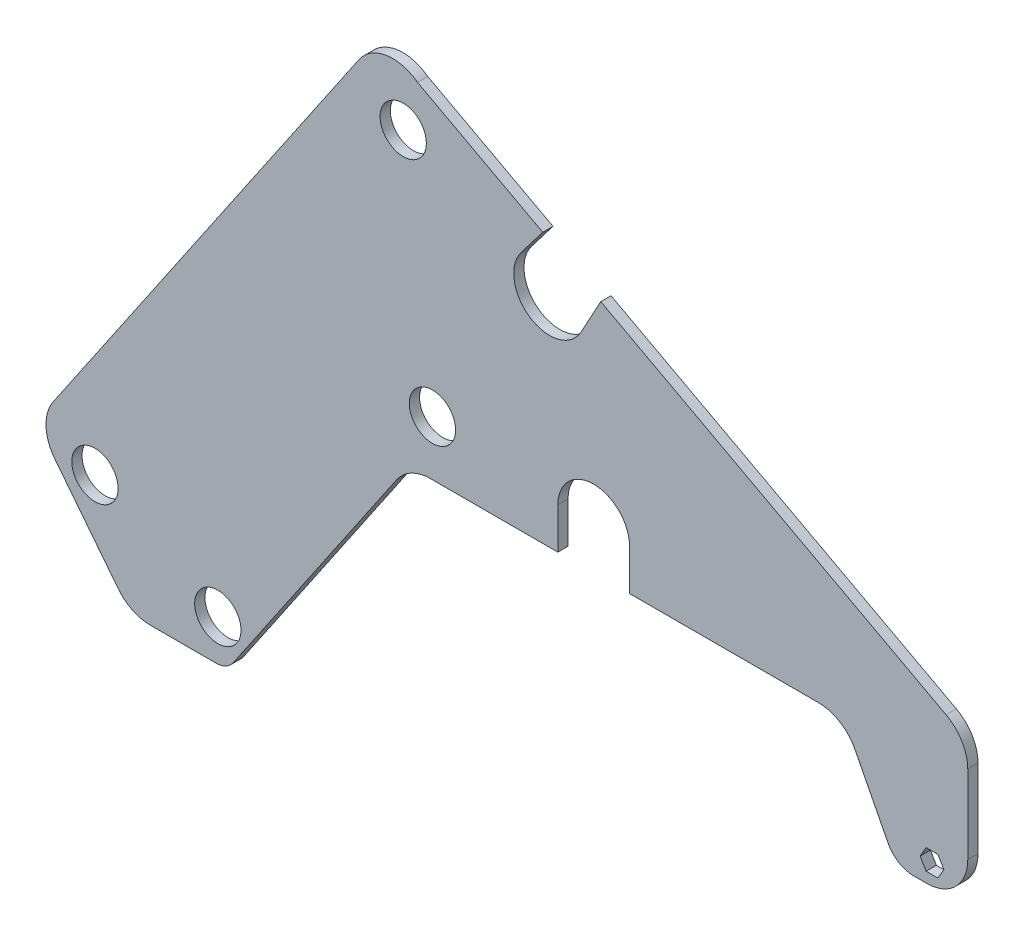
SolidWorks part; units mm, degrees
other "Markup1"
sketch "Sketch1" plane through (-441.7893, 331.8239, 6.35) normal (-0.0431, 0.0102, 0.999) x (0.9985, 0.0354, 0.0427)
sketch "Sketch2" plane through (-413.6701, 343.933, 6.35) normal (-0.0431, 0.0102, 0.999) x (0.9985, 0.0354, 0.0427)
sketch "Sketch3" plane through (-436.3774, 318.5567, 6.35) normal (-0.0431, 0.0102, 0.999) x (0.9985, 0.0354, 0.0427)
sketch "Sketch5" plane through (-436.3774, 318.5567, 6.35) normal (-0.0431, 0.0102, 0.999) x (0.9985, 0.0354, 0.0427)
sketch "Sketch7" plane through (-430.3226, 318.5567, 6.35) normal (-0.0431, 0.0102, 0.999) x (0.9985, 0.0354, 0.0427)
other "Markup2"
sketch "Sketch4" plane through (102.4721, 318.5567, 6.35) normal (0.9364, 0.1073, 0.3342) x (0.3416, -0.0598, -0.9379)
sketch "Sketch6" plane through (102.4721, 318.5567, 6.35) normal (0.9364, 0.1073, 0.3342) x (0.3416, -0.0598, -0.9379)
sketch "Sketch8" plane through (141.2086, 318.5567, 6.35) normal (0.9364, 0.1073, 0.3342) x (0.3416, -0.0598, -0.9379)
ref_plane "Front Plane" through (0, 0, 0) normal (0, 0, 1) x (1, 0, 0)
ref_plane "Top Plane" through (0, 0, 0) normal (0, 1, 0) x (1, 0, 0)
ref_plane "Right Plane" through (0, 0, 0) normal (1, 0, 0) x (0, 0, -1)
sketch "Model" plane through (0, 0, 0) normal (0, 0, 1) x (1, 0, 0)
  line L1 (-191.9011, 104.6502) -> (-112.96, 104.6502)
  line L3 (-314.2383, -55.3595) -> (-212.8994, 93.5413)
  line L4 (-236.3032, 307.4477) -> (-425.9209, 28.8361)
  line L5 (-424.8981, -1.1437) -> (-385.5815, -51.2028)
  line L13 (126.3831, 53.8502) -> (122.717, 60.2002)
  line L14 (122.717, 60.2002) -> (115.3846, 60.2002)
  line L15 (115.3846, 60.2002) -> (111.7185, 53.8502)
  line L16 (111.7185, 53.8502) -> (115.3846, 47.5002)
  line L17 (115.3846, 47.5002) -> (122.717, 47.5002)
  line L18 (122.717, 47.5002) -> (126.3831, 53.8502)
  line L19 (-365.606, -60.914) -> (-324.7375, -60.914)
  line L20 (-871.0211, -88.854) -> (370.1019, -88.854) construction
  line L22 (141.2086, 66.5502) -> (141.2086, 78.8846)
  line L27 (107.6196, 41.1502) -> (115.8086, 41.1502)
  line L28 (-399.9752, 2.586) -> (-323.7752, -35.514) construction
  line L29 (-323.7752, -35.514) -> (-190.7071, 138.5169) construction
  line L30 (-190.7071, 138.5169) -> (-208.8329, 283.4378) construction
  line L31 (-208.8329, 283.4378) -> (-399.9752, 2.586) construction
  line L32 (91.8004, 50.8135) -> (71.26, 90.8456)
  line L33 (48.6612, 104.6502) -> (-11.3966, 104.6502)
  line L34 (141.2086, 78.8846) -> (141.2086, 115.3033)
  line L35 (127.8091, 137.6897) -> (-86.3327, 252.4836)
  line L36 (-86.3327, 252.4836) -> (-98.5536, 230.0471)
  line L37 (-112.96, 130.0502) -> (-112.96, 104.6502)
  line L38 (-122.3008, 271.7648) -> (-135.737, 254.1638)
  line L39 (-68.51, 130.0502) -> (-68.51, 104.6502)
  line L40 (-68.51, 104.6502) -> (-2.1388, 104.6502)
  line L41 (-122.3008, 271.7648) -> (-199.9496, 313.3896)
  arc A3 (121.2475, 59.8082) -> (121.352, 60.2002) centre (96.7586, 66.5502) ccw
  circle A9 centre (-323.7752, -35.514) radius 14.351
  circle A10 centre (-399.9752, 2.586) radius 14.351
  circle A12 centre (-190.7071, 138.5169) radius 14.351
  arc A15 (107.6196, 41.1502) -> (91.8004, 50.8135) centre (107.6196, 58.9302) cw
  arc A21 (-191.9011, 104.6502) -> (-212.8994, 93.5413) centre (-191.9011, 79.2502) ccw
  circle A22 centre (-208.8329, 283.4378) radius 14.351
  circle A24 centre (119.0508, 53.8502) radius 6.35 construction
  arc A31 (-324.7375, -60.914) -> (-314.2383, -55.3595) centre (-324.7375, -48.214) ccw
  arc A40 (114.7422, 48.6129) -> (115.0458, 48.9225) centre (96.7586, 66.5502) ccw
  arc A43 (115.8086, 41.1502) -> (141.2086, 66.5502) centre (115.8086, 66.5502) ccw
  arc A44 (-236.3032, 307.4477) -> (-199.9496, 313.3896) centre (-215.305, 293.1567) cw
  arc A45 (-365.606, -60.914) -> (-385.5815, -51.2028) centre (-365.606, -35.514) cw
  arc A46 (71.26, 90.8456) -> (48.6612, 104.6502) centre (48.6612, 79.2502) ccw
  arc A47 (141.2086, 115.3033) -> (127.8091, 137.6897) centre (115.8086, 115.3033) ccw
  arc A48 (-424.8981, -1.1437) -> (-425.9209, 28.8361) centre (-404.9226, 14.5451) cw
  arc A49 (-135.737, 254.1638) -> (-98.5536, 230.0471) centre (-118.0711, 240.678) ccw
  arc A50 (-68.51, 130.0502) -> (-112.96, 130.0502) centre (-90.735, 130.0502) ccw
  ellipse E0 centre (-551.1692, 173.9527) end of major axis (-591.2054, 216.0961) minor radius 17.278
  point P31 (-177.5612, 330.9695)
  point P34 (100.2935, -12.8222)
  point P43 (-377.9543, -60.914)
  point P55 (96.7586, 41.1502)
  point P59 (174.831, 53.8502)
  point P60 (-205.3388, 104.6502)
  point P64 (-436.3774, 13.472)
  dimension "D3" = 38.1
  dimension "D4" = 104.6502
  dimension "D5" = 76.2
  dimension "D6" = 44.45
  dimension "D7" = 12.7
  dimension "D8" = 28.702
  dimension "D11" = 139.7
  dimension "D12" = 27.94
  dimension "D21" = 124.238
  dimension "D13" = 12.7
  dimension "D16" = 355.6
  dimension "D23" = 25.4
  dimension "D24" = 25.4
  dimension "D26" = 25.4
  dimension "D14" = 406.4
  dimension "D20" = 254
  dimension "D29" = 25.4
  dimension "D31" = 25.4
  dimension "D25" = 88.9
  dimension "D30" = 17.78
  dimension "D32" = 25.4
  dimension "D33" = 25.4
  dimension "D34" = 44.45
  dimension "D35" = 25.4
  dimension "D37" = 44.45
  dimension "D38" = 25.4
  dimension "D9" = 19.05
  dimension "D10" = 146.05
  dimension "D15" = 33.8667
  dimension "D17" = 339.725
  dimension "D18" = 219.075
  dimension "D19" = 50.8
  dimension "D22" = 25.4
  dimension "D27" = 53.2168
  dimension "D28" = 12.7
  dimension "D36" = 100.33
  dimension "D39" = 100.33
extrude "Boss-Extrude1" add sketch "Model" along normal blind 6.35 contours L5 L3 L1 L4 A22 A9 A10 A12 region at (-206.9871, 107.7659, 0)
